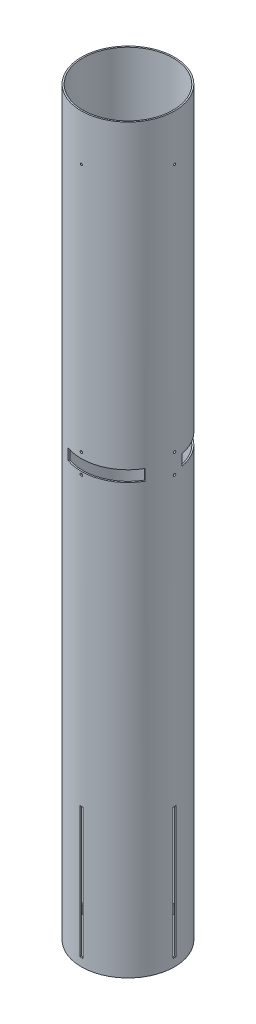
SolidWorks part; units mm, degrees
material "A-Glass Fiber"
ref_plane "Front Plane" through (0, 0, 0) normal (0, 0, 1) x (1, 0, 0)
ref_plane "Top Plane" through (0, 0, 0) normal (0, 1, 0) x (1, 0, 0)
ref_plane "Right Plane" through (0, 0, 0) normal (1, 0, 0) x (0, 0, -1)
sketch "Sketch1" plane through (0, 0, 0) normal (0, 1, 0) x (1, 0, 0)
  circle A0 centre (0, 0) radius 49.53
  circle A1 centre (0, 0) radius 51.1048
  dimension "D1" = 99.06
  dimension "D2" = 102.2096
extrude "Boss-Extrude1" add sketch "Sketch1" along normal blind 812.8
ref_plane "Plane1" through (0, 0, 0) normal (0.7071, 0, 0.7071) x (0.7071, 0, -0.7071)
ref_axis "Axis1" through (0, 812.8, 0) along (0, -1, 0)
sketch "Sketch2" plane through (0, 0, 0) normal (1, 0, 0) x (0, 0, -1)
  line L0 (0, 0) -> (0, 8.89)
  line L1 (1.5875, 8.89) -> (-1.5875, 8.89)
  line L2 (1.5875, 8.89) -> (1.5875, 152.4)
  line L3 (1.5875, 152.4) -> (-1.5875, 152.4)
  line L4 (-1.5875, 8.89) -> (-1.5875, 152.4)
  line L5 (1.5875, 8.89) -> (-1.5875, 152.4) construction
  line L6 (1.5875, 152.4) -> (-1.5875, 8.89) construction
  line L7 (51.1048, 812.8) -> (-51.1048, 812.8) construction
  line L8 (51.1048, 812.8) -> (-51.1048, 812.8)
  line L9 (0, 812.8) -> (0, 488.95)
  line L10 (-51.1048, 0) -> (51.1048, 0) construction
  circle A0 centre (0, 488.95) radius 1.3525
  point P0 (0, 80.645)
  dimension "D4" = 2.7051
  dimension "D1" = 3.175
  dimension "D5" = 488.95
  dimension "D3" = 152.4
  dimension "D2" = 8.89
extrude "Cut-Extrude1" cut sketch "Sketch2" against normal through all contours L4 L1 L2 L3 region at (0, 80.645, 0)
pattern_circular "CirPattern1" count 4 over 360 about axis through (0, 0, 0) along (0, 1, 0) of "Cut-Extrude1" reverse direction yes
extrude "Cut-Extrude2" cut sketch "Sketch2<3>" against normal through all contours A0 region at (0, 488.0207, 0.9293)
sketch "Sketch2<3>" plane through (0, 0, 0) normal (1, 0, 0) x (0, 0, -1) same geometry as "Sketch2"
pattern_circular "CirPattern2" count 4 over 360 about axis through (0, 812.8, 0) along (0, -1, 0) of "Cut-Extrude2"
sketch "Sketch3" plane through (0, 0, 0) normal (0.7071, 0, 0.7071) x (0.7071, 0, -0.7071)
  line L0 (0, 0) -> (0, 127) construction
  circle A0 centre (0, 127) radius 3.175
  dimension "D1" = 6.35
  dimension "D2" = 127
extrude "Cut-Extrude3" cut sketch "Sketch3" against normal through all
sketch "Sketch7" plane through (0, 0, 0) normal (0, 1, 0) x (1, 0, 0)
  line L0 (0, 0) -> (-44.2581, -25.5524)
  line L1 (0, 0) -> (0, 93.232) construction
  line L2 (0, 0) -> (-32.8495, 39.1485)
  line L3 (-51.1048, 0) -> (0, 0) construction
  arc A0 (-51.0869, 1.3525) -> (-51.0869, -1.3525) centre (0, 0) ccw construction
  circle A1 centre (0, 0) radius 49.53 construction
  circle A2 centre (0, 0) radius 51.1048
  circle A3 centre (0, 0) radius 51.1048
  circle A4 centre (0, 0) radius 49.53
  circle A5 centre (0, 0) radius 51.1048 construction
  arc A6 (1.3526, 51.0869) -> (-1.3525, 51.0869) centre (0, 0) ccw construction
  arc A7 (-51.0869, 1.3525) -> (-51.0869, -1.3525) centre (0, 0) ccw
  arc A8 (1.3526, 51.0869) -> (-1.3525, 51.0869) centre (0, 0) ccw
  dimension "D1" = 80
  dimension "D3" = 30
  dimension "D2" = 0
extrude "Cut-Extrude4" cut sketch "Sketch7" against normal blind 12.065 from offset 482.6 contours A4 A3 L0 region at (-43.9137, 0, 24.5741)
pattern_circular "CirPattern3" count 3 over 360 about axis through (0, 812.8, 0) along (0, -1, 0) of "Cut-Extrude4"
pattern_linear "LPattern1" count 2 spacing 21.6916 along (0, -1, 0) of "CirPattern2"
sketch "Sketch8" plane through (0, 0, 0) normal (0, 0, 1) x (1, 0, 0)
  line L0 (49.53, 812.8) -> (-49.53, 812.8) construction
  circle A0 centre (0, 762) radius 1.0922
  dimension "D1" = 2.1844
  dimension "D2" = 50.8
extrude "Cut-Extrude5" cut sketch "Sketch8" against normal through all
pattern_circular "CirPattern4" count 4 over 360 about axis through (0, 812.8, 0) along (0, -1, 0) of "Cut-Extrude5"
sketch "Sketch9" plane through (0, 0, 0) normal (0, 0, 1) x (1, 0, 0)
  line L0 (51.1048, 812.8) -> (-51.1048, 812.8) construction
  point P0 (0, 752.856)
  dimension "D1" = 59.944
hole_wizard "1/2 Clearance Hole4" positions "Sketch17" profile "Sketch18" hole size "1/2" standard "ANSI Inch" end condition through all
sketch "Sketch17" plane through (0, 0, 0) normal (0, 0, 1) x (1, 0, 0)
  point P0 (0, 752.856)
sketch "Sketch18" plane through (0, 752.856, 0) normal (1, 0, 0) x (0, -1, 0)
  line L0 (0, 0) -> (0, 51.1048)
  line L1 (0, 51.1048) -> (6.5481, 51.1048)
  line L2 (6.5481, 51.1048) -> (6.5481, 0)
  line L5 (6.5481, 0) -> (0, 0)
  line L11 (0, -6.35) -> (0, 107.95) construction
  dimension "Thru Hole Dia." = 13.0962
  dimension "Thru Hole Depth" = 51.1048
equation "\"D1@Boss-Extrude1\" = \"Aft_Section_Length\""
equation "\"AB_Coupler_OD_Length\"= 1in"
equation "\"AB_Coupling_Section_Length\"= 0.375in"
equation "\"AB_Coupler_Length\"= \"AB_Coupler_OD_Length\" + \"AB_Coupling_Section_Length\" * 2"
equation "\"AB_Coupler_Num_Screws\"= 4"
equation "\"AB_Coupling_Screw_Diameter\"= 0.1065in"
equation "\"Aft_Section_Length\" = 32in"
equation "\"D4@Sketch2\"=\"AB_Coupling_Screw_Diameter\""
equation "\"D1@CirPattern2\"=\"AB_Coupler_Num_Screws\""
equation "\"Rail_Nut_From_Bottom\"= 5in"
equation "\"Rail_Nut_Diam\"= 0.25in"
equation "\"D1@Sketch3\"=\"Rail_Nut_Diam\""
equation "\"D2@Sketch3\"=\"Rail_Nut_From_Bottom\""
equation "\"AB_BKHD_Thickness\"= 0.375in"
equation "\"AB_Mount_From_Bottom\"= 19.25in"
equation "\"Cutout_Angle\" = 60"
equation "\"Motor_OD\" = 54.4mm"
equation "\"Motor_Length\" = 401mm"
equation "\"Mid_Coupler_Length\" = 12in"
equation "\"AB_Paddle_Height\" = 0.375in"
equation "\"Num_Cutouts\" = 4"
equation "\"AB_Coupler_OD\"= 4.024in"
equation "\"AB_Coupler_ID\"= 3.7in"
equation "\"AB_Coupler_Surface_Diameter\"= 3.899in"
equation "\"AB_Central_Bushing_Length\" = 0.75in"
equation "\"Lead_Screw_Dist\" = 2in"
equation "\"Lead_Screw_Diam\" = 0.375in"
equation "\"Lead_Screw_Length\" = \"Mid_Coupler_Length\" + 2*0.375in + 2*0.5in"
equation "\"Paddle_Pin_Offset\" = 0.25in"
equation "\"Paddle_Pin_Radius\" = 2.25*2/3in"
equation "\"Paddle_Gear_OD\" = 3.2in"
equation "\"Fwd_BKHD_From_Top\" = 18in"
equation "\"Body_Tube_OD\"= 4.024in"
equation "\"Body_Tube_ID\"= 3.90in"
equation "\"Coupler_OD\" = 3.899in"
equation "\"Coupler_ID\" = 3.755in"
equation "\"Fwd_Section_Length\" = 20in"
equation "\"Mid_Section_Length\" = 4in"
equation "\"Aft_Upper_Tube_Length\" = 10in"
equation "\"Aft_Lower_Tube_Length\" = 18in"
equation "\"Nosecone_Coupler_Length\" = 5in"
equation "\"Avionics_Bulkhead_Thickness\" = 0.25in"
equation "\"Avionics_Bulkhead_Lip\" = 0.125in"
equation "\"Avionics_Board_Length\" = \"Mid_Coupler_Length\" - 2*\"Avionics_Bulkhead_Lip\""
equation "\"Lead_Screw_Hole_Diam\" = 0.386in"
equation "\"Centering_Ring_Cutout_Dia\"= 1in"
equation "\"D2@Sketch1\"=\"Body_Tube_OD\""
equation "\"D1@Sketch1\"=\"Body_Tube_ID\""
equation "\"D5@Sketch2\"=\"AB_Mount_From_Bottom\""
equation "\"D19@Cut-Extrude4\"=\"AB_Mount_From_Bottom\"-0.25"
